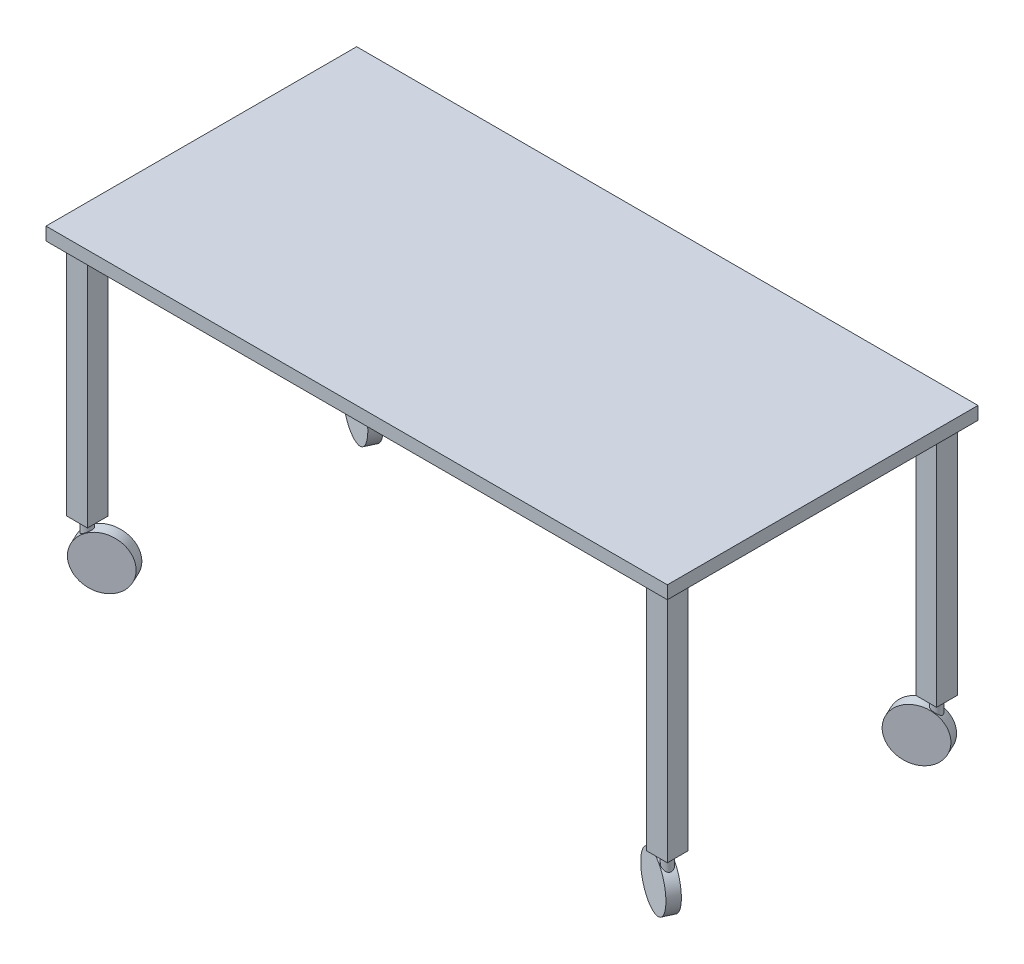
SolidWorks part; units mm, degrees
material "Plain Carbon Steel"
ref_plane "Front Plane" through (0, 0, 0) normal (0, 0, 1) x (1, 0, 0)
ref_plane "Top Plane" through (0, 0, 0) normal (0, 1, 0) x (1, 0, 0)
ref_plane "Right Plane" through (0, 0, 0) normal (1, 0, 0) x (0, 0, -1)
sketch "Sketch1" plane through (0, 0, 0) normal (0, 1, 0) x (1, 0, 0)
  line L1 (-762, -381) -> (762, -381)
  line L2 (-762, -381) -> (-762, 381)
  line L3 (-762, 381) -> (762, 381)
  line L4 (762, -381) -> (762, 381)
  line L5 (-762, -381) -> (762, 381) construction
  line L6 (-762, 381) -> (762, -381) construction
  point P0 (0, 0)
  dimension "D1" = 1524
  dimension "D2" = 762
extrude "Boss-Extrude1" add sketch "Sketch1" against normal blind 31.75
sketch "Sketch2" plane through (0, -31.75, 0) normal (0, -1, 0) x (1, 0, 0)
  line L0 (762, 381) -> (762, -381) construction
  line L1 (-736.6, -355.6) -> (736.6, -355.6) construction
  line L2 (-736.6, -355.6) -> (-736.6, 355.6) construction
  line L3 (-736.6, 355.6) -> (736.6, 355.6) construction
  line L4 (736.6, -355.6) -> (736.6, 355.6) construction
  line L5 (-736.6, -355.6) -> (736.6, 355.6) construction
  line L6 (-736.6, 355.6) -> (736.6, -355.6) construction
  line L7 (-736.6, 355.6) -> (-685.8, 355.6)
  line L8 (-736.6, 355.6) -> (-736.6, 304.8)
  line L9 (-736.6, 304.8) -> (-685.8, 304.8)
  line L10 (-685.8, 355.6) -> (-685.8, 304.8)
  line L11 (-736.6, -355.6) -> (-685.8, -355.6)
  line L12 (-736.6, -355.6) -> (-736.6, -304.8)
  line L13 (-736.6, -304.8) -> (-685.8, -304.8)
  line L14 (-685.8, -355.6) -> (-685.8, -304.8)
  line L15 (736.6, -355.6) -> (685.8, -355.6)
  line L16 (736.6, -355.6) -> (736.6, -304.8)
  line L17 (736.6, -304.8) -> (685.8, -304.8)
  line L18 (685.8, -355.6) -> (685.8, -304.8)
  line L19 (736.6, 355.6) -> (685.8, 355.6)
  line L20 (736.6, 355.6) -> (736.6, 304.8)
  line L21 (736.6, 304.8) -> (685.8, 304.8)
  line L22 (685.8, 355.6) -> (685.8, 304.8)
  line L23 (-762, 381) -> (762, 381) construction
  point P0 (0, 0)
  dimension "D1" = 50.8
  dimension "D2" = 50.8
  dimension "D3" = 25.4
  dimension "D4" = 25.4
extrude "Boss-Extrude2" add sketch "Sketch2" along normal blind 584.2
sketch "Sketch3" plane through (0, -615.95, 0) normal (0, -1, 0) x (1, 0, 0)
  line L1 (-711.2, -330.2) -> (711.2, -330.2) construction
  line L2 (-711.2, -330.2) -> (-711.2, 330.2) construction
  line L3 (-711.2, 330.2) -> (711.2, 330.2) construction
  line L4 (711.2, -330.2) -> (711.2, 330.2) construction
  line L5 (-711.2, -330.2) -> (711.2, 330.2) construction
  line L6 (-711.2, 330.2) -> (711.2, -330.2) construction
  line L7 (685.8, 355.6) -> (736.6, 304.8) construction
  circle A0 centre (711.2, 330.2) radius 12.7
  circle A1 centre (711.2, -330.2) radius 12.7
  circle A2 centre (-711.2, -330.2) radius 12.7
  circle A3 centre (-711.2, 330.2) radius 12.7
  point P8 (0, 0)
  dimension "D1" = 25.4
extrude "Boss-Extrude3" add sketch "Sketch3" along normal blind 101.6
ref_axis "Axis1" through (711.2, -717.55, 330.2) along (0, 1, 0)
ref_axis "Axis2" through (0, 35.8775, 0) along (0, -1, 0)
ref_plane "Plane1" through (0, 0, 0) normal (-0.4211, 0, 0.907) x (0.907, 0, 0.4211)
sketch "Sketch4" plane through (0, 0, 0) normal (-0.4211, 0, 0.907) x (0.907, 0, 0.4211)
  line L0 (784.1157, -717.55) -> (784.1157, -615.95) construction
  circle A0 centre (752.3657, -698.5) radius 63.5
  point P4 (752.3657, -762)
  dimension "D2" = 127
  dimension "D1" = 31.75
  dimension "D3" = 762
extrude "Boss-Extrude4" add sketch "Sketch4" along normal mid plane 28.575
mirror "Mirror1" about plane through (0, 0, 0) normal (0, 0, 1) of "Boss-Extrude4"
mirror "Mirror2" about plane through (0, 0, 0) normal (1, 0, 0) of "Boss-Extrude4", "Mirror1"
